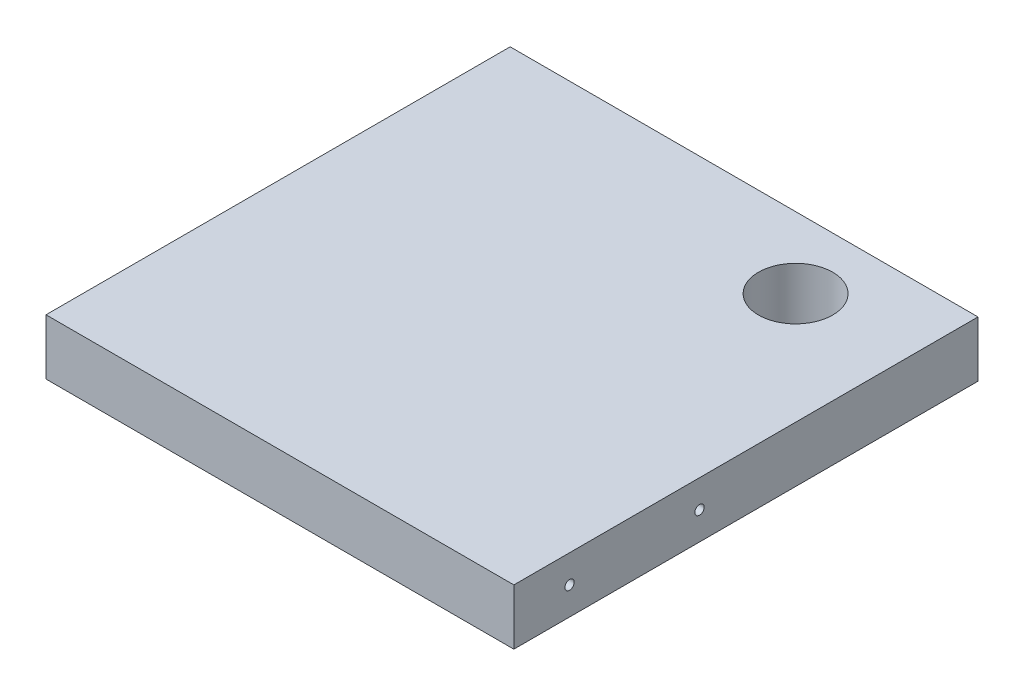
SolidWorks part; units mm, degrees
material "Beech"
ref_plane "Front Plane" through (0, 0, 0) normal (0, 0, 1) x (1, 0, 0)
ref_plane "Top Plane" through (0, 0, 0) normal (0, 1, 0) x (1, 0, 0)
ref_plane "Right Plane" through (0, 0, 0) normal (1, 0, 0) x (0, 0, -1)
sketch "Sketch1" plane through (0, 0, 0) normal (0, 0, 1) x (1, 0, 0)
  line L0 (80.01, 5194.3) -> (80.01, 5232.4) construction
  line L1 (-80.01, 5846.1044) -> (80.01, 5846.1044)
  line L2 (-80.01, 5846.1044) -> (-80.01, 5827.0544)
  line L3 (-80.01, 5827.0544) -> (80.01, 5827.0544)
  line L4 (80.01, 5846.1044) -> (80.01, 5827.0544)
  line L5 (-80.01, 5194.3) -> (-80.01, 5334) construction
  line L6 (-80.01, 5827.0544) -> (-99.06, 5827.0544) construction
  dimension "D1" = 19.05
extrude "Boss-Extrude1" add sketch "Sketch1" along normal offset from surface (158.75 mm away) 82.55 offset beyond the face yes
hole_wizard "Hole1" positions "Sketch2" profile "Sketch3" legacy
sketch "Sketch2" plane through (0, 0, -19.05) normal (0, 0, -1) x (-1, 0, 0)
  line L1 (0, 5194.3) -> (0, 5935.98) construction
  line L9 (80.01, 5836.5794) -> (-80.01, 5836.5794) construction
  point P1 (0.1622, 5756.275)
  point P4 (0, 5926.455)
  point P16 (-203.2, 5926.455)
  point P28 (-406.4, 5926.455)
  point P31 (-406.5622, 5756.275)
  point P43 (-203.3622, 5756.275)
  point P55 (-359.618, 5737.225)
  point P61 (-428.6139, 5737.225)
  point P64 (-421.2578, 5578.475)
  point P70 (-319.6578, 5578.475)
  point P82 (-116.4578, 5578.475)
  point P85 (-424.0726, 5559.425)
  point P91 (-358.1042, 5559.425)
  point P94 (-418.2303, 5400.675)
  point P100 (-316.6303, 5400.675)
  point P112 (-113.4303, 5400.675)
  point P115 (-419.5313, 5381.625)
  point P121 (-356.5904, 5381.625)
  point P124 (-415.2028, 5222.875)
  point P130 (-313.6028, 5222.875)
  point P144 (-110.4028, 5222.875)
  point P147 (-414.9901, 5203.825)
  point P153 (-355.0767, 5203.825)
  point P159 (355.0767, 5203.825)
  point P161 (414.9901, 5203.825)
  point P162 (110.4028, 5222.875)
  point P166 (313.6028, 5222.875)
  point P168 (415.2028, 5222.875)
  point P169 (356.5904, 5381.625)
  point P171 (419.5313, 5381.625)
  point P172 (113.4303, 5400.675)
  point P176 (316.6303, 5400.675)
  point P178 (418.2303, 5400.675)
  point P179 (358.1042, 5559.425)
  point P181 (424.0726, 5559.425)
  point P182 (116.4578, 5578.475)
  point P186 (319.6578, 5578.475)
  point P188 (421.2578, 5578.475)
  point P189 (428.6139, 5737.225)
  point P191 (359.618, 5737.225)
  point P195 (203.3622, 5756.275)
  point P199 (406.5622, 5756.275)
  point P200 (406.4, 5926.455)
  point P204 (203.2, 5926.455)
  point P208 (-0.1622, 5756.275)
  point P252 (0, 5836.5794)
  point P254 (-60.96, 5836.5794)
  point P256 (60.96, 5836.5794)
sketch "Sketch3" plane through (-0.1622, 5756.275, -19.05) normal (1, 0, 0) x (0, 1, 0)
  line L0 (0, 0) -> (0, 32.346)
  line L1 (0, 32.346) -> (0.9919, 31.75)
  line L2 (0.9919, 31.75) -> (0.9919, 4.7029)
  line L3 (0.9919, 4.7029) -> (5.08, 0)
  line L4 (5.08, 0) -> (0, 0)
  line L5 (0, -14.3089) -> (0, 102.4216) construction
  line L6 (0, 32.346) -> (-0.9919, 31.75) construction
  line L7 (-0.9919, 4.7029) -> (-5.08, 0) construction
  dimension "Diameter" = 1.9837
  dimension "Depth" = 31.75
  dimension "C-Sink Diameter" = 10.16
  dimension "C-Sink Angle" = 82
  dimension "Drill Angle" = 118
hole_wizard "Hole3" positions "Sketch6" profile "Sketch7" legacy
sketch "Sketch6" plane through (99.06, 0, -2683.51) normal (1, 0, 0) x (0, 0, -1)
  line L0 (-2759.71, 5836.5794) -> (-2842.26, 5836.5794) construction
  point P13 (-2823.21, 5836.5794)
  point P15 (-2778.76, 5836.5794)
sketch "Sketch7" plane through (99.06, 5836.5794, 95.25) normal (0, 1, 0) x (0, 0, -1)
  line L0 (0, 0) -> (0, 32.7039)
  line L1 (0, 32.7039) -> (1.5875, 31.75)
  line L2 (1.5875, 31.75) -> (1.5875, 4.0177)
  line L3 (1.5875, 4.0177) -> (5.08, 0)
  line L4 (5.08, 0) -> (0, 0)
  line L5 (0, -14.3089) -> (0, 102.4216) construction
  line L6 (0, 32.7039) -> (-1.5875, 31.75) construction
  line L7 (-1.5875, 4.0177) -> (-5.08, 0) construction
  dimension "Diameter" = 3.175
  dimension "Depth" = 31.75
  dimension "C-Sink Diameter" = 10.16
  dimension "C-Sink Angle" = 82
  dimension "Drill Angle" = 118
hole_wizard "Hole4" positions "Sketch8" profile "Sketch9" legacy
sketch "Sketch8" plane through (-99.06, 0, -2683.51) normal (-1, 0, 0) x (0, 0, 1)
  line L0 (2759.71, 5836.5794) -> (2842.26, 5836.5794) construction
  point P12 (2823.21, 5836.5794)
  point P14 (2778.76, 5836.5794)
sketch "Sketch9" plane through (-99.06, 5836.5794, 95.25) normal (0, 1, 0) x (0, 0, 1)
  line L0 (0, 0) -> (0, 32.7039)
  line L1 (0, 32.7039) -> (1.5875, 31.75)
  line L2 (1.5875, 31.75) -> (1.5875, 4.0177)
  line L3 (1.5875, 4.0177) -> (5.08, 0)
  line L4 (5.08, 0) -> (0, 0)
  line L5 (0, -14.3089) -> (0, 102.4216) construction
  line L6 (0, 32.7039) -> (-1.5875, 31.75) construction
  line L7 (-1.5875, 4.0177) -> (-5.08, 0) construction
  dimension "Diameter" = 3.175
  dimension "Depth" = 31.75
  dimension "C-Sink Diameter" = 10.16
  dimension "C-Sink Angle" = 82
  dimension "Drill Angle" = 118
hole_wizard "1 (1) Diameter Hole1" positions "Sketch10" profile "Sketch11" hole size "1" standard "ANSI Inch" end condition up to next
sketch "Sketch10" plane through (0, 5827.0544, 0) normal (0, -1, 0) x (-1, 0, 0)
  line L0 (80.01, 0) -> (-80.01, 0) construction
  line L1 (-80.01, -158.75) -> (-80.01, 0) construction
  point P0 (-41.91, -24.2952)
  dimension "D1" = 24.2952
  dimension "D2" = 38.1
sketch "Sketch11" plane through (41.91, 5827.0544, 24.2952) normal (1, 0, 0) x (0, 0, -1)
  line L0 (0, 0) -> (0, 19.05)
  line L1 (0, 19.05) -> (12.7, 19.05)
  line L2 (12.7, 19.05) -> (12.7, 0)
  line L5 (12.7, 0) -> (0, 0)
  line L11 (0, -6.35) -> (0, 107.95) construction
  dimension "Thru Hole Dia." = 25.4
  dimension "Thru Hole Depth" = 19.05
